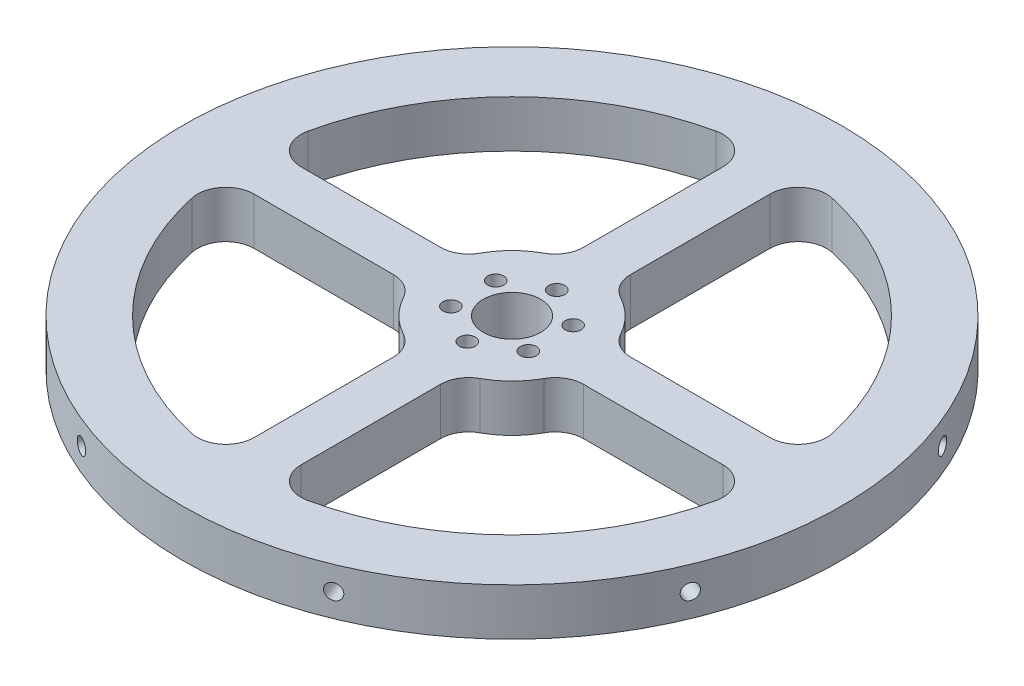
SolidWorks part; units mm, degrees
material "6061-T6 (SS)"
ref_plane "Front Plane" through (0, 0, 0) normal (0, 0, 1) x (1, 0, 0)
ref_plane "Top Plane" through (0, 0, 0) normal (0, 1, 0) x (1, 0, 0)
ref_plane "Right Plane" through (0, 0, 0) normal (1, 0, 0) x (0, 0, -1)
sketch "Sketch2" plane through (0, 0, 0) normal (0, 1, 0) x (1, 0, 0)
  circle A1 centre (0, 0) radius 70
  dimension "D1" = 140
extrude "Boss-Extrude1" add sketch "Sketch2" along normal mid plane 10
sketch "Sketch3" plane through (0, 5, 0) normal (0, 1, 0) x (1, 0, 0)
  line L0 (0, 0) -> (70, 0) construction
  line L1 (5, -57) -> (-5, -57)
  line L2 (57, 5) -> (0, 5)
  line L3 (57, 5) -> (57, -5)
  line L4 (57, -5) -> (0, -5)
  line L5 (0, 5) -> (0, -5)
  line L6 (57, 5) -> (0, -5) construction
  line L7 (57, -5) -> (0, 5) construction
  line L8 (-5, -57) -> (-5, 0)
  line L9 (5, -57) -> (5, 0)
  line L10 (5, 0) -> (-5, 0)
  line L11 (-57, -5) -> (-57, 5)
  line L12 (-57, 5) -> (0, 5)
  line L13 (-57, -5) -> (0, -5)
  line L14 (0, -5) -> (0, 5)
  line L15 (-5, 57) -> (5, 57)
  line L16 (5, 57) -> (5, 0)
  line L17 (-5, 57) -> (-5, 0)
  line L18 (-5, 0) -> (5, 0)
  circle A0 centre (0, 0) radius 57
  circle A1 centre (0, 0) radius 17
  circle A2 centre (0, 0) radius 57
  circle A3 centre (0, 0) radius 57
  circle A4 centre (0, 0) radius 57
  point P3 (28.5, 0)
  point P29 (0, 0)
  dimension "D1" = 114
  dimension "D2" = 34
  dimension "D3" = 10
  dimension "D4" = 4
extrude "Cut-Extrude1" cut sketch "Sketch3" against normal blind 10 contours A1 L17 A0 L12 | A1 L13 A0 L8 | A1 L9 A0 L4 | A1 L2 A0 L16 region at (27.1395, 5, 27.1395) region at (-27.1395, 5, 27.1395) region at (27.1395, 5, -27.1395) region at (-27.1395, 5, -27.1395)
sketch "Sketch6" plane through (0, 5, 0) normal (0, 1, 0) x (1, 0, 0)
  circle A0 centre (0, 0) radius 6.1
  dimension "D1" = 12.2
extrude "Cut-Extrude3" cut sketch "Sketch6" against normal through all
sketch "Sketch7" plane through (0, 5, 0) normal (0, 1, 0) x (1, 0, 0)
  circle A0 centre (0, 0) radius 9.5 construction
  circle A1 centre (0, 9.5) radius 1.7
  circle A2 centre (8.2272, 4.75) radius 1.7
  circle A3 centre (0, 0) radius 9.5 construction
  circle A4 centre (8.2272, -4.75) radius 1.7
  circle A5 centre (0, 0) radius 9.5 construction
  circle A6 centre (0, -9.5) radius 1.7
  circle A7 centre (0, 0) radius 9.5 construction
  circle A8 centre (-8.2272, -4.75) radius 1.7
  circle A9 centre (0, 0) radius 9.5 construction
  circle A10 centre (-8.2272, 4.75) radius 1.7
  circle A11 centre (0, 0) radius 9.5 construction
  point P22 (0, 0)
  dimension "D1" = 19
  dimension "D2" = 3.4
  dimension "D3" = 6
extrude "Cut-Extrude4" cut sketch "Sketch7" against normal through all
fillet "Fillet1" radius 6 16 edges at (16.2481, 0, 5) (56.7803, 0, 5) (56.7803, 0, -5) (16.2481, 0, -5) (5, 0, -16.2481) (5, 0, -56.7803) (-5, 0, -56.7803) (-5, 0, -16.2481) (-16.2481, 0, -5) (-56.7803, 0, -5) (-56.7803, 0, 5) (-16.2481, 0, 5) (-5, 0, 16.2481) (-5, 0, 56.7803) (5, 0, 56.7803) (5, 0, 16.2481)
ref_axis "Axis1" through (0, 5, 0) along (0, -1, 0)
ref_plane "Plane1" through (0, 0, 0) normal (-0.3827, 0, -0.9239) x (0, -1, 0)
ref_plane "Plane2" through (64.6716, 0, -26.7878) normal (0.9239, 0, -0.3827) x (-0.3827, 0, -0.9239)
sketch "Sketch10" plane through (64.6716, 0, -26.7878) normal (0.9239, 0, -0.3827) x (-0.3827, 0, -0.9239)
  circle A0 centre (0, 0) radius 1.65
  dimension "D1" = 3.3
extrude "Cut-Extrude5" cut sketch "Sketch10" against normal blind 10
pattern_circular "CirPattern2" count 8 over 360 about axis through (0, 5, 0) along (0, -1, 0) of "Cut-Extrude5" reverse direction yes
equation "\"D1@Sketch2\"=\"WHL_WheelOD\""
equation "\"D1@Boss-Extrude1\"=\"WHL_WheelThk\""
equation "\"____ GENERATED PART EXPORTS ____\" = 0"
equation "\"SYS_VersionTag\" = 2"
equation "\"WHL_UsesOnePieceWebbedWheel\" = 1"
equation "\"WHL_WheelOD\" = 140mm"
equation "\"WHL_WheelID\" = 114mm"
equation "\"WHL_WheelThk\" = 10mm"
equation "\"WHL_WheelRadius\" = 70mm"
equation "\"WHL_CenterPadOD\" = 34mm"
equation "\"WHL_HubPilotHoleDia\" = 12.2mm"
equation "\"WHL_HubMountBCD\" = 19mm"
equation "\"WHL_HubMountCount\" = 6"
equation "\"WHL_HubMountClearDia\" = 3.4mm"
equation "\"WHL_WebCount\" = 4"
equation "\"WHL_WebWidth\" = 10mm"
equation "\"WHL_WebFilletR\" = 6mm"
equation "\"WHL_RimInnerDia\" = 114mm"
equation "\"WHL_TuneStationCount\" = 8"
equation "\"WHL_TuneStationOffsetDeg\" = 22.5"
equation "\"WHL_TuneThreadNominal\" = 4mm"
equation "\"WHL_TuneTapDrillDia\" = 3.3mm"
equation "\"WHL_TuneTapDepth\" = 10mm"
equation "\"WHL_TuneUsesFlushRadialSetScrews\" = 1"
equation "\"WHL_TuneSetScrewNominalLength\" = 8mm"
equation "\"WHL_TuneMinimumInnerWall\" = 2.5mm"
equation "\"D1@Sketch3\"=\"WHL_WheelID\""
equation "\"D2@Sketch3\"=\"WHL_CenterPadOD\""
equation "\"D3@Sketch3\"=\"WHL_WebWidth\""
equation "\"D1@Sketch6\"=\"WHL_HubPilotHoleDia\""
equation "\"D1@Sketch7\"=\"WHL_HubMountBCD\""
equation "\"D2@Sketch7\"=\"WHL_HubMountClearDia\""
equation "\"D1@Fillet1\"=\"WHL_WebFilletR\""
equation "\"D1@Sketch10\"=\"WHL_TuneTapDrillDia\""
equation "\"D1@Cut-Extrude5\"=\"WHL_TuneTapDepth\""
equation "\"D1@CirPattern2\"=\"WHL_TuneStationCount\""
